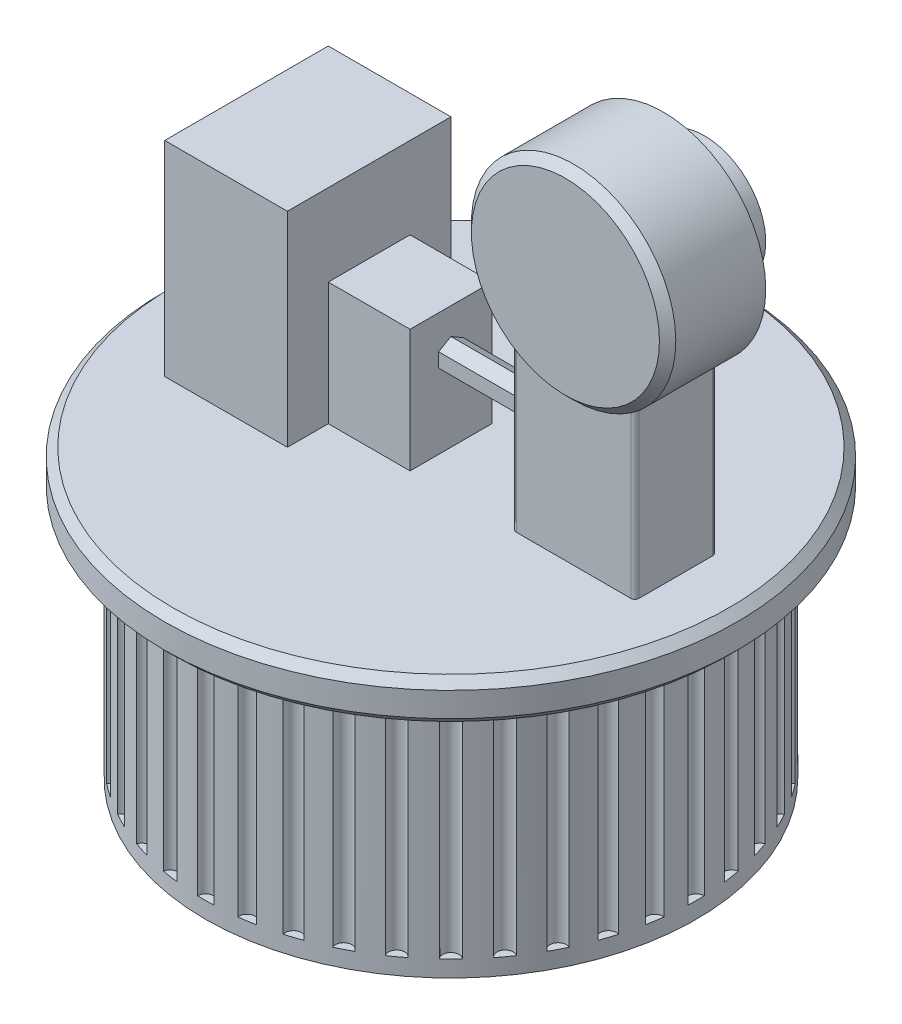
SolidWorks part; units mm, degrees
ref_plane "Płaszczyzna przednia" through (0, 0, 0) normal (0, 0, 1) x (1, 0, 0)
ref_plane "Płaszczyzna górna" through (0, 0, 0) normal (0, 1, 0) x (1, 0, 0)
ref_plane "Płaszczyzna prawa" through (0, 0, 0) normal (1, 0, 0) x (0, 0, -1)
sketch "Sketch1" plane through (0, 0, 0) normal (0, 1, 0) x (1, 0, 0)
  circle A0 centre (0, 0) radius 30
  dimension "D1" = 60
extrude "Boss-Extrude1" add sketch "Sketch1" along normal blind 2
ref_plane "Plane1" through (0, 2, 0) normal (0, -1, 0) x (-1, 0, 0)
sketch "Sketch2" plane through (0, 2, 0) normal (0, -1, 0) x (-1, 0, 0)
  circle A0 centre (0, 0) radius 30 construction
  arc A1 (-0.9999, 29.9833) -> (-3.7029, 29.7706) centre (0, 0) ccw
  arc A2 (-0.9999, 29.9833) -> (0.9999, 29.9833) centre (0, 30) ccw
  arc A3 (3.7029, 29.7706) -> (5.678, 29.4578) centre (4.693, 29.6307) ccw
  arc A4 (8.3144, 28.8248) -> (10.2163, 28.2069) centre (9.2705, 28.5317) ccw
  arc A5 (12.7213, 27.1693) -> (14.503, 26.2614) centre (13.6197, 26.7302) ccw
  arc A6 (16.8149, 24.8447) -> (18.4327, 23.6693) centre (17.6336, 24.2705) ccw
  arc A7 (20.4944, 21.9084) -> (21.9084, 20.4944) centre (21.2132, 21.2132) ccw
  arc A8 (23.6693, 18.4327) -> (24.8447, 16.8149) centre (24.2705, 17.6336) ccw
  arc A9 (26.2614, 14.503) -> (27.1693, 12.7213) centre (26.7302, 13.6197) ccw
  arc A10 (28.2069, 10.2163) -> (28.8248, 8.3144) centre (28.5317, 9.2705) ccw
  arc A11 (29.4578, 5.678) -> (29.7706, 3.7029) centre (29.6307, 4.693) ccw
  arc A12 (29.9833, 0.9999) -> (29.9833, -0.9999) centre (30, 0) ccw
  arc A13 (29.7706, -3.7029) -> (29.4578, -5.678) centre (29.6307, -4.693) ccw
  arc A14 (28.8248, -8.3144) -> (28.2069, -10.2163) centre (28.5317, -9.2705) ccw
  arc A15 (27.1693, -12.7213) -> (26.2614, -14.503) centre (26.7302, -13.6197) ccw
  arc A16 (24.8447, -16.8149) -> (23.6693, -18.4327) centre (24.2705, -17.6336) ccw
  arc A17 (21.9084, -20.4944) -> (20.4944, -21.9084) centre (21.2132, -21.2132) ccw
  arc A18 (18.4327, -23.6693) -> (16.8149, -24.8447) centre (17.6336, -24.2705) ccw
  arc A19 (14.503, -26.2614) -> (12.7213, -27.1693) centre (13.6197, -26.7302) ccw
  arc A20 (10.2163, -28.2069) -> (8.3144, -28.8248) centre (9.2705, -28.5317) ccw
  arc A21 (5.678, -29.4578) -> (3.7029, -29.7706) centre (4.693, -29.6307) ccw
  arc A22 (0.9999, -29.9833) -> (-0.9999, -29.9833) centre (0, -30) ccw
  arc A23 (-3.7029, -29.7706) -> (-5.678, -29.4578) centre (-4.693, -29.6307) ccw
  arc A24 (-8.3144, -28.8248) -> (-10.2163, -28.2069) centre (-9.2705, -28.5317) ccw
  arc A25 (-12.7213, -27.1693) -> (-14.503, -26.2614) centre (-13.6197, -26.7302) ccw
  arc A26 (-16.8149, -24.8447) -> (-18.4327, -23.6693) centre (-17.6336, -24.2705) ccw
  arc A27 (-20.4944, -21.9084) -> (-21.9084, -20.4944) centre (-21.2132, -21.2132) ccw
  arc A28 (-23.6693, -18.4327) -> (-24.8447, -16.8149) centre (-24.2705, -17.6336) ccw
  arc A29 (-26.2614, -14.503) -> (-27.1693, -12.7213) centre (-26.7302, -13.6197) ccw
  arc A30 (-28.2069, -10.2163) -> (-28.8248, -8.3144) centre (-28.5317, -9.2705) ccw
  arc A31 (-29.4578, -5.678) -> (-29.7706, -3.7029) centre (-29.6307, -4.693) ccw
  arc A32 (-29.9833, -0.9999) -> (-29.9833, 0.9999) centre (-30, 0) ccw
  arc A33 (-29.7706, 3.7029) -> (-29.4578, 5.678) centre (-29.6307, 4.693) ccw
  arc A34 (-28.8248, 8.3144) -> (-28.2069, 10.2163) centre (-28.5317, 9.2705) ccw
  arc A35 (-27.1693, 12.7213) -> (-26.2614, 14.503) centre (-26.7302, 13.6197) ccw
  arc A36 (-24.8447, 16.8149) -> (-23.6693, 18.4327) centre (-24.2705, 17.6336) ccw
  arc A37 (-21.9084, 20.4944) -> (-20.4944, 21.9084) centre (-21.2132, 21.2132) ccw
  arc A38 (-18.4327, 23.6693) -> (-16.8149, 24.8447) centre (-17.6336, 24.2705) ccw
  arc A39 (-14.503, 26.2614) -> (-12.7213, 27.1693) centre (-13.6197, 26.7302) ccw
  arc A40 (-10.2163, 28.2069) -> (-8.3144, 28.8248) centre (-9.2705, 28.5317) ccw
  arc A41 (-5.678, 29.4578) -> (-3.7029, 29.7706) centre (-4.693, 29.6307) ccw
  arc A42 (-5.678, 29.4578) -> (-8.3144, 28.8248) centre (0, 0) ccw
  arc A43 (-10.2163, 28.2069) -> (-12.7213, 27.1693) centre (0, 0) ccw
  arc A44 (-14.503, 26.2614) -> (-16.8149, 24.8447) centre (0, 0) ccw
  arc A45 (-18.4327, 23.6693) -> (-20.4944, 21.9084) centre (0, 0) ccw
  arc A46 (-21.9084, 20.4944) -> (-23.6693, 18.4327) centre (0, 0) ccw
  arc A47 (-24.8447, 16.8149) -> (-26.2614, 14.503) centre (0, 0) ccw
  arc A48 (-27.1693, 12.7213) -> (-28.2069, 10.2163) centre (0, 0) ccw
  arc A49 (-28.8248, 8.3144) -> (-29.4578, 5.678) centre (0, 0) ccw
  arc A50 (-29.7706, 3.7029) -> (-29.9833, 0.9999) centre (0, 0) ccw
  arc A51 (-29.9833, -0.9999) -> (-29.7706, -3.7029) centre (0, 0) ccw
  arc A52 (-29.4578, -5.678) -> (-28.8248, -8.3144) centre (0, 0) ccw
  arc A53 (-28.2069, -10.2163) -> (-27.1693, -12.7213) centre (0, 0) ccw
  arc A54 (-26.2614, -14.503) -> (-24.8447, -16.8149) centre (0, 0) ccw
  arc A55 (-23.6693, -18.4327) -> (-21.9084, -20.4944) centre (0, 0) ccw
  arc A56 (-20.4944, -21.9084) -> (-18.4327, -23.6693) centre (0, 0) ccw
  arc A57 (-16.8149, -24.8447) -> (-14.503, -26.2614) centre (0, 0) ccw
  arc A58 (-12.7213, -27.1693) -> (-10.2163, -28.2069) centre (0, 0) ccw
  arc A59 (-8.3144, -28.8248) -> (-5.678, -29.4578) centre (0, 0) ccw
  arc A60 (-3.7029, -29.7706) -> (-0.9999, -29.9833) centre (0, 0) ccw
  arc A61 (0.9999, -29.9833) -> (3.7029, -29.7706) centre (0, 0) ccw
  arc A62 (5.678, -29.4578) -> (8.3144, -28.8248) centre (0, 0) ccw
  arc A63 (10.2163, -28.2069) -> (12.7213, -27.1693) centre (0, 0) ccw
  arc A64 (14.503, -26.2614) -> (16.8149, -24.8447) centre (0, 0) ccw
  arc A65 (18.4327, -23.6693) -> (20.4944, -21.9084) centre (0, 0) ccw
  arc A66 (21.9084, -20.4944) -> (23.6693, -18.4327) centre (0, 0) ccw
  arc A67 (27.1693, -12.7213) -> (28.2069, -10.2163) centre (0, 0) ccw
  arc A68 (28.8248, -8.3144) -> (29.4578, -5.678) centre (0, 0) ccw
  arc A69 (29.9833, 0.9999) -> (29.7706, 3.7029) centre (0, 0) ccw
  arc A70 (29.4578, 5.678) -> (28.8248, 8.3144) centre (0, 0) ccw
  arc A71 (28.2069, 10.2163) -> (27.1693, 12.7213) centre (0, 0) ccw
  arc A72 (26.2614, 14.503) -> (24.8447, 16.8149) centre (0, 0) ccw
  arc A73 (23.6693, 18.4327) -> (21.9084, 20.4944) centre (0, 0) ccw
  arc A74 (20.4944, 21.9084) -> (18.4327, 23.6693) centre (0, 0) ccw
  arc A75 (16.8149, 24.8447) -> (14.503, 26.2614) centre (0, 0) ccw
  arc A76 (12.7213, 27.1693) -> (10.2163, 28.2069) centre (0, 0) ccw
  arc A77 (8.3144, 28.8248) -> (5.678, 29.4578) centre (0, 0) ccw
  arc A78 (3.7029, 29.7706) -> (0.9999, 29.9833) centre (0, 0) ccw
  arc A79 (29.9833, -0.9999) -> (29.7706, -3.7029) centre (0, 0) cw
  arc A80 (26.2614, -14.503) -> (24.8447, -16.8149) centre (0, 0) cw
  point P125 (0, 0)
  dimension "D1" = 2
  dimension "D2" = 40
extrude "Boss-Extrude2" add sketch "Sketch2" against normal blind 28
sketch "Sketch3" plane through (0, 30, 0) normal (0, 1, 0) x (1, 0, 0)
  circle A0 centre (0, 0) radius 35
  dimension "D1" = 70
extrude "Boss-Extrude3" add sketch "Sketch3" along normal blind 5
sketch "Sketch4" plane through (0, 35, 0) normal (0, 1, 0) x (1, 0, 0)
  line L0 (-35, 0) -> (35, 0) construction
  line L1 (0, 35) -> (0, -35) construction
  line L3 (-10, -10) -> (-25, -10)
  line L4 (-10, -10) -> (-10, 10)
  line L5 (-10, 10) -> (-25, 10)
  line L6 (-25, -10) -> (-25, 10)
  line L7 (-10, -10) -> (-25, 10) construction
  line L8 (-10, 10) -> (-25, -10) construction
  line L9 (0, -5) -> (-10, -5)
  line L10 (0, -5) -> (0, 5)
  line L11 (0, 5) -> (-10, 5)
  line L12 (-10, -5) -> (-10, 5)
  line L13 (0, -5) -> (-10, 5) construction
  line L14 (0, 5) -> (-10, -5) construction
  line L15 (12.5, 5) -> (27.5, 5)
  line L16 (12.5, 5) -> (12.5, -5)
  line L17 (12.5, -5) -> (27.5, -5)
  line L18 (27.5, 5) -> (27.5, -5)
  line L19 (12.5, 5) -> (27.5, -5) construction
  line L20 (12.5, -5) -> (27.5, 5) construction
  circle A0 centre (0, 0) radius 35 construction
  point P8 (-17.5, 0)
  point P13 (-5, 0)
  point P18 (20, 0)
  dimension "D1" = 15
  dimension "D2" = 20
  dimension "D3" = 10
  dimension "D4" = 10
  dimension "D5" = 10
  dimension "D6" = 15
  dimension "D7" = 10
  dimension "D8" = 15
extrude "Boss-Extrude4" add sketch "Sketch4" along normal blind 25 contours L6 L3 L4 L5 region at (-17.5, 35, 0)
extrude "Boss-Extrude5" add sketch "Sketch4<3>" along normal blind 15 contours L11 L12 L9 L10
sketch "Sketch4<3>" plane through (0, 35, 0) normal (0, 1, 0) x (1, 0, 0) same geometry as "Sketch4"
extrude "Boss-Extrude6" add sketch "Sketch4<4>" along normal blind 20 contours L15 L18 L17 L16
sketch "Sketch4<4>" plane through (0, 35, 0) normal (0, 1, 0) x (1, 0, 0) same geometry as "Sketch4"
sketch "Sketch5" plane through (0, 0, 5) normal (0, 0, 1) x (1, 0, 0)
  line L0 (12.5, 55) -> (27.5, 55) construction
  line L1 (12.5, 55) -> (27.5, 55) construction
  line L2 (20, 55) -> (20, 65) construction
  circle A0 centre (20, 65) radius 12.5
  dimension "D1" = 25
  dimension "D2" = 10
extrude "Boss-Extrude7" add sketch "Sketch5" against normal blind 11 and the other way blind 1
sketch "Sketch6" plane through (0, 0, -6) normal (0, 0, -1) x (-1, 0, 0)
  circle A0 centre (-20, 65) radius 7.5
  dimension "D1" = 15
extrude "Boss-Extrude8" add sketch "Sketch6" along normal blind 5
sketch "Sketch7" plane through (0, 0, 0) normal (1, 0, 0) x (0, 0, -1)
  line L0 (-5, 50) -> (5, 35) construction
  line L1 (5, 35) -> (5, 50) construction
  line L2 (5, 50) -> (-5, 50) construction
  line L3 (-5, 50) -> (-5, 35) construction
  line L4 (-5, 35) -> (5, 35) construction
  line L5 (5, 50) -> (-5, 35) construction
  line L6 (0, 42.5) -> (0, 45) construction
  line L8 (0, 46.7321) -> (-1.5, 45.866)
  line L9 (-1.5, 45.866) -> (-1.5, 44.134)
  line L10 (-1.5, 44.134) -> (0, 43.2679)
  line L11 (0, 43.2679) -> (1.5, 44.134)
  line L12 (1.5, 44.134) -> (1.5, 45.866)
  line L13 (1.5, 45.866) -> (0, 46.7321)
  circle A0 centre (0, 45) radius 1.5 construction
  dimension "D2" = 3
  dimension "D1" = 2.5
extrude "Boss-Extrude9" add sketch "Sketch7" along normal up to next
chamfer "Chamfer1" distance 1 angle 45 2 edges at (0, 30, 35) (0, 35, 35)
fillet "Fillet1" radius 0.5 4 edges at (12.5, 45, -5) (27.5, 45, -5) (12.5, 45, 5) (27.5, 45, 5)
chamfer "Chamfer2" distance 1 angle 45 1 edges at (32.5, 65, 6)
sketch "Sketch8" plane through (0, 0, 0) normal (0, 0, 1) x (1, 0, 0)
  line L0 (0, 30) -> (0, 0) construction
  line L1 (-0.9999, 30) -> (0.9999, 30) construction
  point P0 (0, 16)
  point P8 (0, 0)
  dimension "D1" = 16
